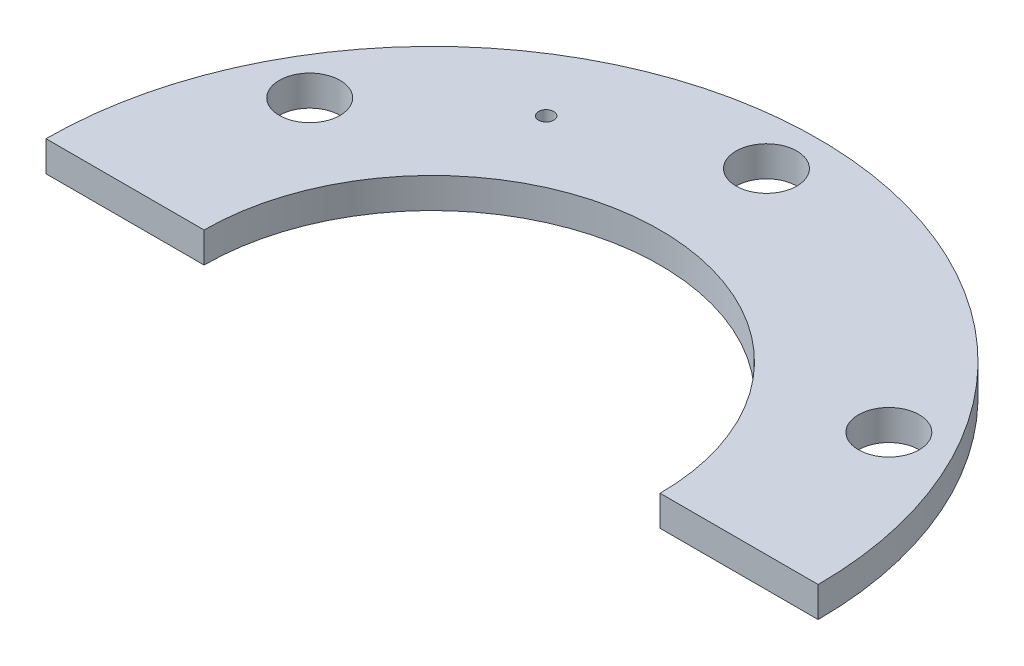
SolidWorks part; units mm, degrees
material "ABS"
ref_plane "Front Plane" through (0, 0, 0) normal (0, 0, 1) x (1, 0, 0)
ref_plane "Top Plane" through (0, 0, 0) normal (0, 1, 0) x (1, 0, 0)
ref_plane "Right Plane" through (0, 0, 0) normal (1, 0, 0) x (0, 0, -1)
sketch "Sketch1" plane through (0, 0, 0) normal (0, 1, 0) x (1, 0, 0)
  circle A0 centre (0, 0) radius 12.7
  dimension "D1" = 25.4
extrude "Boss-Extrude1" add sketch "Sketch1" along normal blind 1
sketch "Sketch19" plane through (0, 1, 0) normal (0, 1, 0) x (1, 0, 0)
  circle A0 centre (0, 11) radius 1
  circle A1 centre (9.5263, 5.5) radius 1
  circle A2 centre (9.5263, -5.5) radius 1
  circle A3 centre (0, -11) radius 1
  circle A4 centre (-9.5263, -5.5) radius 1
  circle A5 centre (-9.5263, 5.5) radius 1
  point P13 (0, 0)
  dimension "D1" = 2
  dimension "D2" = 11
  dimension "D3" = 6
extrude "Cut-Extrude1" cut sketch "Sketch19" against normal through all both and the other way through all
sketch "Sketch20" plane through (0, 1, 0) normal (0, 1, 0) x (1, 0, 0)
  circle A0 centre (0, 0) radius 7.5
  dimension "D1" = 15
extrude "Cut-Extrude2" cut sketch "Sketch20" against normal through all both and the other way through all
sketch "Sketch21" plane through (0, 0, 0) normal (0, 0, 1) x (1, 0, 0)
  line L1 (-36.7533, 32.3113) -> (29.1209, 32.3113)
  line L2 (-36.7533, 32.3113) -> (-36.7533, -19.668)
  line L3 (-36.7533, -19.668) -> (29.1209, -19.668)
  line L4 (29.1209, 32.3113) -> (29.1209, -19.668)
extrude "Cut-Extrude3" cut sketch "Sketch21" along normal through all
sketch "Sketch22" plane through (0, 1, 0) normal (0, 1, 0) x (1, 0, 0)
  line L0 (-9.5263, 5.5) -> (0, 11)
  line L1 (-5.125, 8.8768) -> (0, 0) construction
  circle A0 centre (-5.125, 8.8768) radius 0.25
  point P7 (-4.7631, 8.25)
  dimension "D1" = 0.5
  dimension "D2" = 10.25
  dimension "D3" = 0
extrude "Cut-Extrude4" cut sketch "Sketch22" against normal through all both and the other way through all contours L0 A0 | L1 L0 A0 | L0 L1 A0 region at (-5.125, 1, -8.8768)
